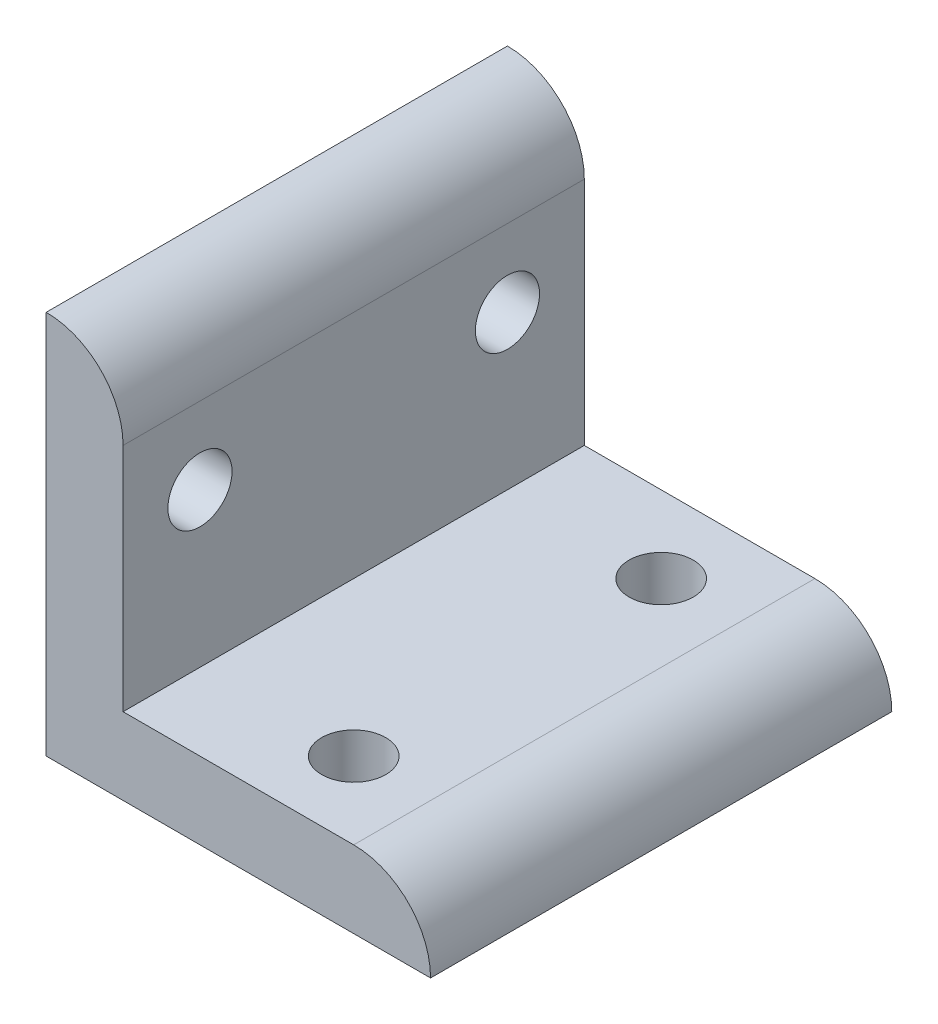
SolidWorks part; units mm, degrees
material "AISI 1045 Steel, cold drawn"
ref_plane "Front Plane" through (0, 0, 0) normal (0, 0, 1) x (1, 0, 0)
ref_plane "Top Plane" through (0, 0, 0) normal (0, 1, 0) x (1, 0, 0)
ref_plane "Right Plane" through (0, 0, 0) normal (1, 0, 0) x (0, 0, -1)
sketch "Sketch1" plane through (0, 0, 0) normal (0, 0, 1) x (1, 0, 0)
  line L0 (0, 0) -> (31.75, 0)
  line L1 (31.75, 0) -> (31.75, 6.35)
  line L2 (31.75, 6.35) -> (6.35, 6.35)
  line L3 (6.35, 6.35) -> (6.35, 31.75)
  line L4 (6.35, 31.75) -> (0, 31.75)
  line L5 (0, 31.75) -> (0, 0)
  dimension "D1" = 31.75
  dimension "D2" = 6.35
extrude "Boss-Extrude1" add sketch "Sketch1" along normal blind 38.1
fillet "Fillet1" radius 6.35 2 edges at (31.75, 6.35, 19.05) (6.35, 31.75, 19.05)
hole_wizard "M5 Clearance Hole1" positions "Sketch2" profile "Sketch3" hole size "M5" standard "ANSI Metric" end condition up to next
sketch "Sketch2" plane through (6.35, 0, 0) normal (1, 0, 0) x (0, 0, -1)
  line L0 (-31.75, 19.05) -> (-6.35, 19.05) construction
  line L2 (-38.1, 31.75) -> (0, 31.75) construction
  line L3 (-38.1, 0) -> (0, 0) construction
  point P0 (-31.75, 19.05)
  point P2 (-6.35, 19.05)
  point P11 (-19.05, 31.75)
  point P12 (-19.05, 19.05)
  dimension "D1" = 25.4
  dimension "D2" = 19.05
sketch "Sketch3" plane through (6.35, 19.05, 31.75) normal (0, 1, 0) x (0, 0, -1)
  line L0 (0, 0) -> (0, 6.35)
  line L1 (0, 6.35) -> (2.65, 6.35)
  line L2 (2.65, 6.35) -> (2.65, 0)
  line L5 (2.65, 0) -> (0, 0)
  line L11 (0, -6.35) -> (0, 107.95) construction
  dimension "Thru Hole Dia." = 5.3
  dimension "Thru Hole Depth" = 6.35
ref_plane "Plane1" through (0, 0, 0) normal (-0.7071, 0.7071, 0) x (0.7071, 0.7071, 0)
mirror "Mirror1" about plane through (0, 0, 0) normal (-0.7071, 0.7071, 0) of "M5 Clearance Hole1"
